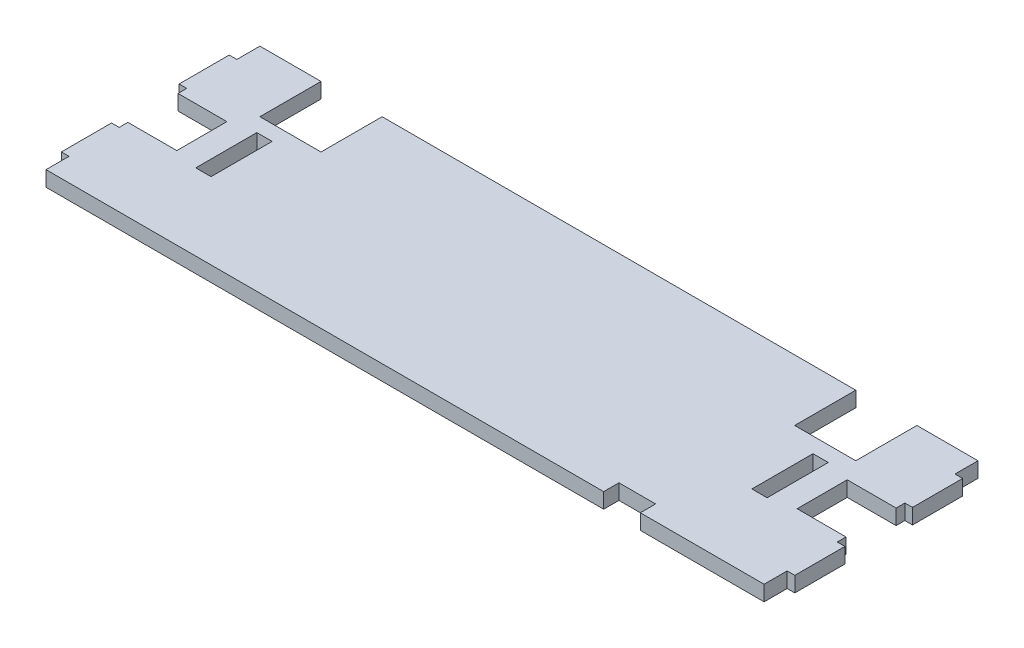
SolidWorks part; units mm, degrees
ref_plane "Front Plane" through (0, 0, 0) normal (0, 0, 1) x (1, 0, 0)
ref_plane "Top Plane" through (0, 0, 0) normal (0, 1, 0) x (1, 0, 0)
ref_plane "Right Plane" through (0, 0, 0) normal (1, 0, 0) x (0, 0, -1)
sketch "Sketch1" plane through (0, 0, 0) normal (0, 1, 0) x (1, 0, 0)
  line L0 (0, 72.39) -> (0, -44.45) construction
  line L1 (149.225, -44.45) -> (97.79, -44.45)
  line L2 (149.225, -44.45) -> (149.225, -34.8747)
  line L3 (149.225, 44.45) -> (123.825, 44.45)
  line L4 (-149.225, -44.45) -> (-149.225, -34.8747)
  line L5 (149.225, -44.45) -> (-149.225, 44.45) construction
  line L6 (149.225, 44.45) -> (-149.225, -44.45) construction
  line L7 (149.225, 10.414) -> (128.905, 10.414)
  line L9 (149.225, -10.414) -> (128.905, -10.414)
  line L10 (128.905, 10.414) -> (128.905, -10.414)
  line L11 (-123.825, 44.45) -> (-149.225, 44.45)
  line L13 (-149.225, -10.414) -> (-128.905, -10.414)
  line L14 (-128.905, 10.414) -> (-128.905, -10.414)
  line L15 (-149.225, 10.414) -> (-128.905, 10.414)
  line L17 (-127, 0) -> (127, 0) construction
  line L18 (-149.225, 14.0467) -> (-152.4, 14.0467)
  line L20 (-149.225, 34.8747) -> (-152.4, 34.8747)
  line L21 (-152.4, 14.0467) -> (-152.4, 34.8747)
  line L22 (-149.225, -34.8747) -> (-152.4, -34.8747)
  line L23 (-152.4, -14.0467) -> (-152.4, -34.8747)
  line L24 (-149.225, -14.0467) -> (-152.4, -14.0467)
  line L27 (149.225, -14.0467) -> (152.4, -14.0467)
  line L28 (152.4, -14.0467) -> (152.4, -34.8747)
  line L29 (149.225, -34.8747) -> (152.4, -34.8747)
  line L30 (149.225, 34.8747) -> (152.4, 34.8747)
  line L31 (152.4, 14.0467) -> (152.4, 34.8747)
  line L32 (149.225, 14.0467) -> (152.4, 14.0467)
  line L34 (-149.225, 34.8747) -> (-149.225, 44.45)
  line L35 (-149.225, -14.0467) -> (-149.225, -10.414)
  line L36 (149.225, 34.8747) -> (149.225, 44.45)
  line L37 (149.225, -14.0467) -> (149.225, -10.414)
  line L38 (-149.225, 10.414) -> (-149.225, 14.0467)
  line L39 (149.225, 10.414) -> (149.225, 14.0467)
  line L40 (-123.825, 44.45) -> (-123.825, 19.05)
  line L41 (-123.825, 19.05) -> (-98.425, 19.05)
  line L42 (-98.425, 44.45) -> (-98.425, 19.05)
  line L44 (98.425, 44.45) -> (98.425, 19.05)
  line L45 (98.425, 19.05) -> (123.825, 19.05)
  line L46 (123.825, 44.45) -> (123.825, 19.05)
  line L47 (98.425, 44.45) -> (-98.425, 44.45)
  line L48 (82.55, -44.45) -> (-149.225, -44.45)
  line L50 (82.55, -44.45) -> (82.55, -38.1)
  line L51 (82.55, -38.1) -> (97.79, -38.1)
  line L52 (97.79, -44.45) -> (97.79, -38.1)
  point P0 (0, 0)
  point P6 (127, 0)
  dimension "D1" = 298.45
  dimension "D2" = 88.9
  dimension "D3" = 20.828
  dimension "D5" = 3.175
  dimension "D6" = 20.828
  dimension "D4" = 20.32
  dimension "D7" = 25.4
  dimension "D8" = 25.4
  dimension "D9" = 25.4
  dimension "D10" = 25.4
  dimension "D12" = 25.4
  dimension "D11" = 25.4
  dimension "D13" = 304.8
  dimension "D14" = 15.24
  dimension "D15" = 6.35
  dimension "D16" = 231.775
extrude "Boss-Extrude1" add sketch "Sketch1" along normal mid plane 6.35
sketch "Sketch2" plane through (0, 0, 0) normal (0, 1, 0) x (1, 0, 0)
  line L1 (112.395, -12.7) -> (118.745, -12.7)
  line L2 (112.395, -12.7) -> (112.395, 12.7)
  line L3 (112.395, 12.7) -> (118.745, 12.7)
  line L4 (118.745, -12.7) -> (118.745, 12.7)
  line L5 (112.395, -12.7) -> (118.745, 12.7) construction
  line L6 (112.395, 12.7) -> (118.745, -12.7) construction
  line L13 (128.905, -10.414) -> (128.905, 10.414) construction
  line L15 (-112.395, -12.7) -> (-112.395, 12.7)
  line L16 (-112.395, -12.7) -> (-118.745, -12.7)
  line L17 (-118.745, -12.7) -> (-118.745, 12.7)
  line L18 (-112.395, 12.7) -> (-118.745, 12.7)
  point P0 (115.57, 0)
  point P10 (128.905, 0)
  dimension "D2" = 10.16
  dimension "D4" = 25.4
  dimension "D5" = 6.35
extrude "Cut-Extrude1" cut sketch "Sketch2" against normal through all both and the other way through all
equation "\"length\"= \"Avionics_Board_Length\""
equation "\"width\"=3.5"
equation "\"height\"= 0.25"
equation "\"D2@Sketch1\"=\"width\""
equation "\"eyebolt width\"= 0.82"
equation "\"eyebolt length\"= 0.8"
equation "\"D3@Sketch1\"=\"eyebolt width\""
equation "\"D4@Sketch1\"=\"eyebolt length\""
equation "\"lead screw holder height\"= 2.76"
equation "\"distance from holders to board\"=0.4"
equation "\"Mid_Coupler_Length\" = 12in"
equation "\"Avionics_Bulkhead_Thickness\" = 0.25in"
equation "\"Avionics_Bulkhead_Lip\" = 0.125in"
equation "\"Avionics_Board_Length\" = \"Mid_Coupler_Length\" - 2*\"Avionics_Bulkhead_Lip\""
equation "\"Body_Tube_OD\"= 4.024in"
equation "\"D1@Sketch1\"=\"length\""
